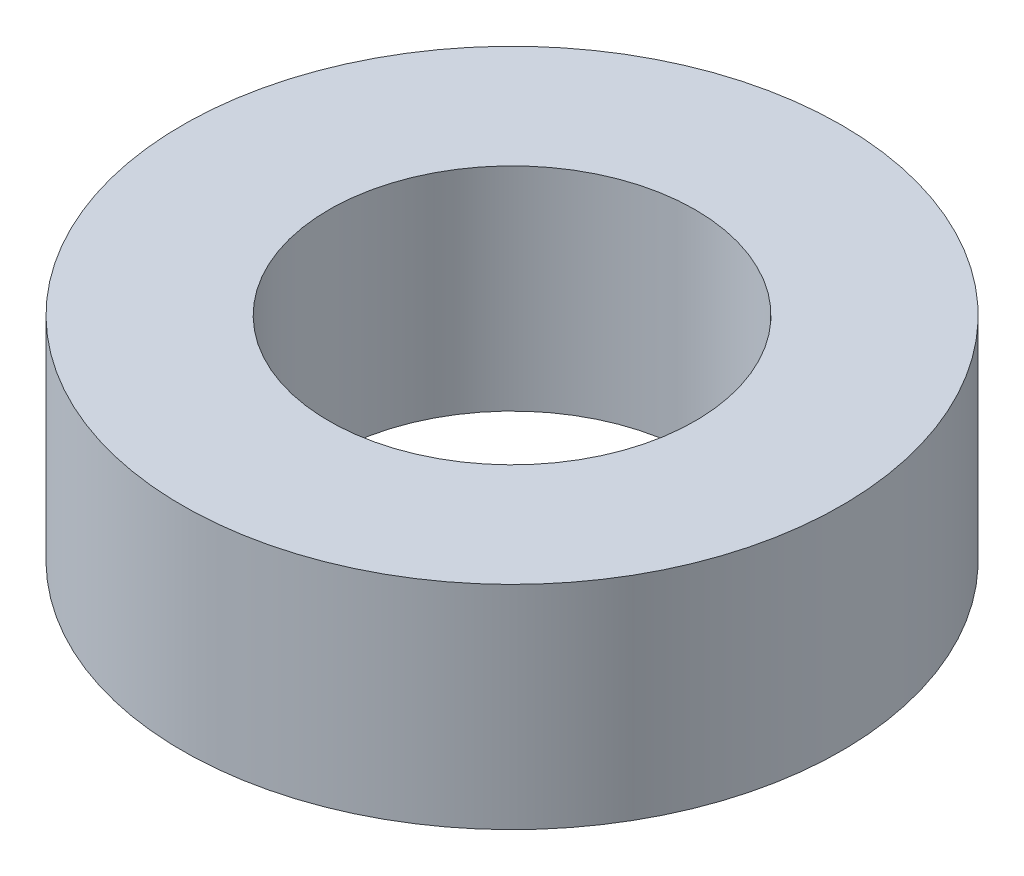
SolidWorks part; units mm, degrees
ref_plane "Front Plane" through (0, 0, 0) normal (0, 0, 1) x (1, 0, 0)
ref_plane "Top Plane" through (0, 0, 0) normal (0, 1, 0) x (1, 0, 0)
ref_plane "Right Plane" through (0, 0, 0) normal (1, 0, 0) x (0, 0, -1)
sketch "Sketch1" plane through (0, 0, 0) normal (0, 1, 0) x (1, 0, 0)
  circle A0 centre (0, 0) radius 45
  dimension "FLANGE_OD" = 90
extrude "Boss-Extrude1" add sketch "Sketch1" along normal blind 29
sketch "Sketch2" plane through (0, 0, 0) normal (0, 1, 0) x (1, 0, 0)
  circle A0 centre (0, 0) radius 25
  dimension "BORE_D" = 50
extrude "Cut-Extrude1" cut sketch "Sketch2" along normal through all
sketch "Sketch3" plane through (0, 29, 0) normal (0, 1, 0) x (1, 0, 0)
  circle A0 centre (0, 0) radius 17.1952 construction
  circle A1 centre (-17.1952, 0) radius 2.4127
  dimension "BOLT_D" = 4.8255
  dimension "BOLT_PCD" = 34.3904
extrude "Cut-Extrude2" cut sketch "Sketch3" against normal blind 25.5549 rebuild error yes
pattern_circular "CirPattern1" count 8 over 360 rebuild error yes
